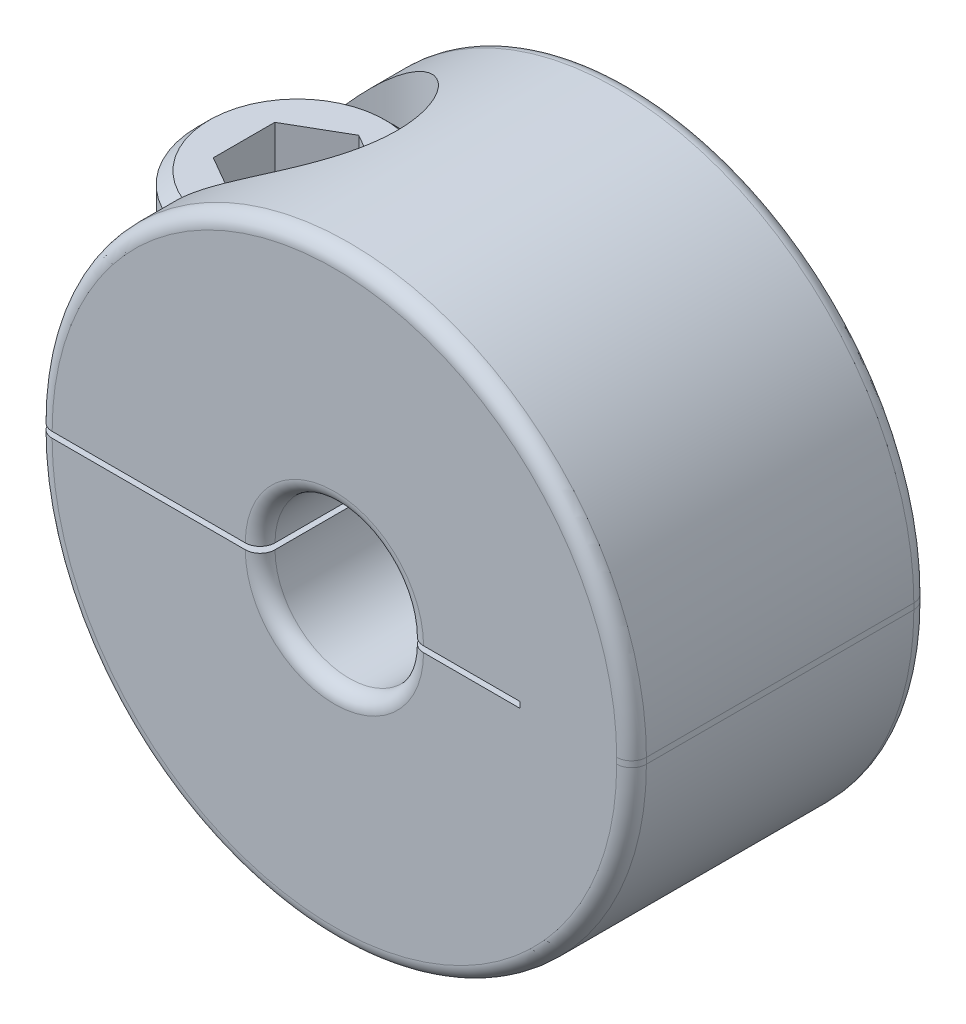
SolidWorks part; units mm, degrees
ref_plane "Front Plane" through (0, 0, 0) normal (0, 0, 1) x (1, 0, 0)
ref_plane "Top Plane" through (0, 0, 0) normal (0, 1, 0) x (1, 0, 0)
ref_plane "Right Plane" through (0, 0, 0) normal (1, 0, 0) x (0, 0, -1)
sketch "Sketch1" plane through (0, 0, 0) normal (0, 0, 1) x (1, 0, 0)
  line L0 (-6.35, 0) -> (-1.5875, 0) construction
  line L1 (-6.35, 0.0635) -> (-1.5875, 0.0635)
  line L2 (-6.35, -0.0635) -> (-1.5875, -0.0635)
  line L3 (1.5875, 0.0635) -> (6.35, 0.0635) construction
  line L4 (1.5875, -0.0635) -> (6.35, -0.0635) construction
  line L5 (0, 0) -> (0, 6.35) construction
  line L6 (6.35, 0.0635) -> (6.35, -0.0635)
  line L7 (1.5875, 0.0635) -> (3.9688, 0.0635)
  line L8 (3.9688, 0.0635) -> (3.9688, -0.0635)
  line L10 (3.9688, -0.0635) -> (1.5875, -0.0635)
  circle A0 centre (0, 0) radius 6.35 construction
  circle A1 centre (0, 0) radius 1.5875 construction
  arc A2 (-6.35, 0.0635) -> (6.35, 0.0635) centre (0, 0.0635) cw
  arc A3 (-6.35, -0.0635) -> (6.35, -0.0635) centre (0, -0.0635) ccw
  arc A4 (-1.5875, 0.0635) -> (1.5875, 0.0635) centre (0, 0.0635) cw
  arc A5 (-1.5875, -0.0635) -> (1.5875, -0.0635) centre (0, -0.0635) ccw
  point P4 (6.35, 0)
  dimension "Bore Dia" = 3.175
  dimension "OD" = 12.7
  dimension "Separation" = 0.127
extrude "Extrude1" add sketch "Sketch1" along normal mid plane 6.35
sketch "Sketch4" plane through (0, 0, 0) normal (0, 0, 1) x (1, 0, 0)
  line L0 (-3.9687, 6.4135) -> (-1.8351, 6.4135)
  line L1 (-1.8351, 6.4135) -> (-1.8351, 1.4859)
  line L2 (-1.8351, 1.4859) -> (-2.5463, 1.4859)
  line L3 (-2.5463, 1.4859) -> (-2.5463, -6.4135)
  line L4 (-2.5463, -6.4135) -> (-3.9687, -6.4135)
  line L5 (-3.9687, -6.4135) -> (-3.9687, 6.4135)
  line L6 (-1.8351, 4.3307) -> (-6.1023, 4.3307) construction
  line L7 (-3.9687, 6.4135) -> (-3.9687, 8.9535) construction
  line L8 (-1.8351, 6.4135) -> (0, 6.4135) construction
  line L9 (0, -6.4135) -> (-2.5463, -6.4135) construction
  line L10 (-6.35, 0) -> (-1.5875, 0) construction
  line L11 (-6.35, 0.0635) -> (-1.5875, 0.0635) construction
  circle A0 centre (0, 0) radius 6.35 construction
  arc A1 (6.35, 0.0635) -> (-6.35, 0.0635) centre (0, 0.0635) ccw construction
  circle A2 centre (0, 0) radius 1.5875 construction
  arc A3 (-6.35, -0.0635) -> (6.35, -0.0635) centre (0, -0.0635) ccw construction
  point P13 (-3.9687, 0)
  point P19 (-3.9687, 0)
  point P20 (-3.9687, 4.3307)
  dimension "D1" = 2.8448
  dimension "D2" = 4.7625
  dimension "D3" = 1.4224
  dimension "D4" = 4.2672
  dimension "D5" = 2.54
  dimension "Screw Dia" = 2.8448
revolve "Cut-Revolve1" cut sketch "Sketch4" angle 360 about L5
sketch "Sketch6" plane through (0, 0, 0) normal (0, 0, 1) x (1, 0, 0)
  line L0 (-3.9687, 4.3307) -> (-1.8351, 4.3307)
  line L1 (-1.8351, 4.3307) -> (-6.1023, 4.3307) construction
  line L2 (-1.8351, 4.3307) -> (-1.8351, 1.4859)
  line L3 (-1.8351, 1.4859) -> (-2.5463, 1.4859)
  line L4 (-2.5463, 1.4859) -> (-2.5463, -4.2037)
  line L5 (-2.5463, 1.4859) -> (-2.5463, -6.4135) construction
  line L6 (-2.5463, -4.2037) -> (-3.9687, -4.2037)
  line L7 (-3.9687, -6.4135) -> (-3.9687, 6.4135) construction
  line L8 (-3.9687, -4.2037) -> (-3.9687, 4.3307)
  line L9 (-2.5463, -4.2037) -> (-5.3911, -4.2037) construction
  dimension "Head Ht" = 2.8448
  dimension "Screw Lg" = 8.5344
revolve "Revolve1" add sketch "Sketch6" angle 360 about L8
sketch "Sketch7" plane through (0, 4.3307, 0) normal (0, 1, 0) x (-1, 0, 0)
  line L1 (3.9687, -1.314) -> (5.1067, -0.657)
  line L2 (5.1067, -0.657) -> (5.1067, 0.657)
  line L3 (5.1067, 0.657) -> (3.9687, 1.314)
  line L4 (3.9687, 1.314) -> (2.8308, 0.657)
  line L5 (2.8308, 0.657) -> (2.8308, -0.657)
  line L6 (2.8308, -0.657) -> (3.9687, -1.314)
  circle A0 centre (3.9687, 0) radius 1.1379 construction
  dimension "D1" = 2.2758
extrude "Cut-Extrude2" cut sketch "Sketch7" against normal blind 1.4224
fillet "Fillet1" radius 0.3175 8 edges at (0, 1.651, -3.175) (0, 1.651, 3.175) (0, 6.4135, -3.175) (0, 6.4135, 3.175) (0, -6.4135, -3.175) (0, -6.4135, 3.175) (6.35, 0, -3.175) (6.35, 0, 3.175)
fillet "Fillet2" radius 0.3175 2 edges at (0, -1.651, -3.175) (0, -1.651, 3.175)
chamfer "Chamfer2" distance 0.254 angle 45 1 edges at (-3.9687, 4.3307, -2.1336)
equation "\"D1@Sketch4\" = \"Screw Dia@Sketch4\""
equation "\"D4@Sketch4\" = \"Screw Dia@Sketch4\"*1.5"
equation "\"D1@Sketch7\" = \"Screw Dia@Sketch4\"*.8"
equation "\"D1@Cut-Extrude2\" = \"Head Ht@Sketch6\"/2"
equation "\"D3@Sketch4\" = \"D1@Sketch4\"*.5"
equation "\"D1@Fillet1\" = \"Width@Extrude1\"*.05"
equation "\"D1@Fillet2\" = \"D1@Fillet1\""
equation "\"Screw Lg@Sketch6\" = \"Head Ht@Sketch6\"*3"
equation "\"Separation@Sketch1\" = \"OD@Sketch1\"*.01"
